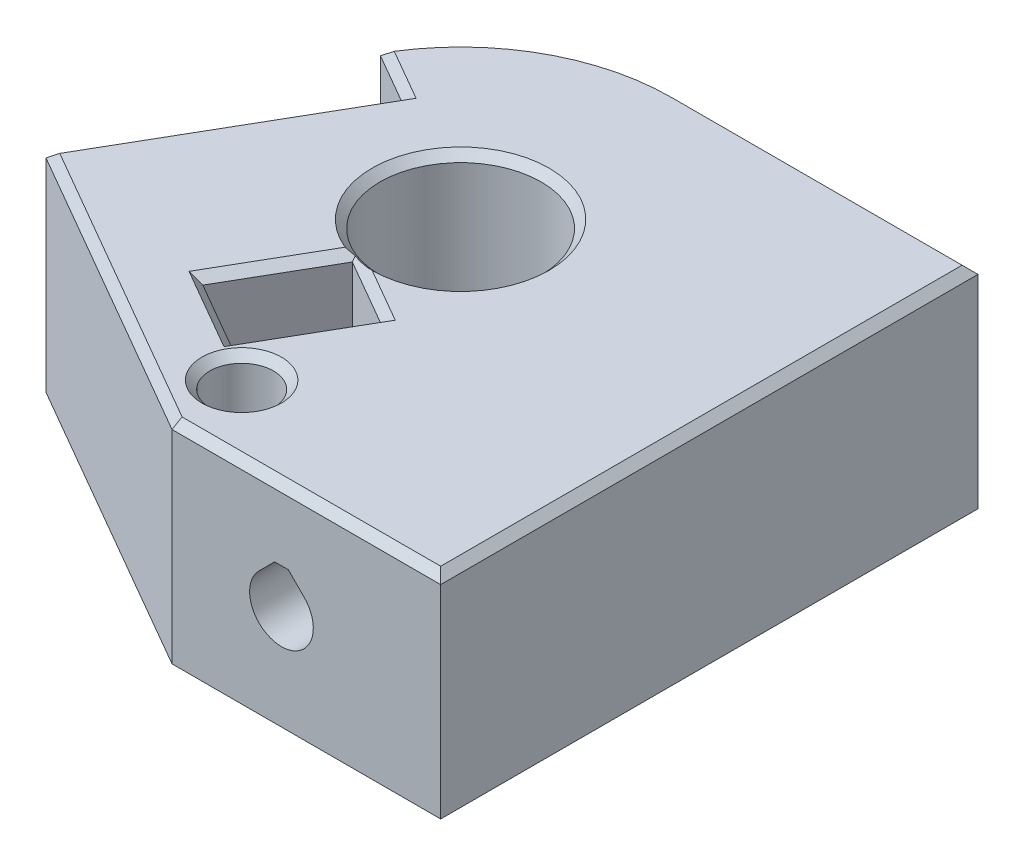
SolidWorks part; units mm, degrees
material "Custom Plastic"
ref_plane "Front Plane" through (0, 0, 0) normal (0, 0, 1) x (1, 0, 0)
ref_plane "Top Plane" through (0, 0, 0) normal (0, 1, 0) x (1, 0, 0)
ref_plane "Right Plane" through (0, 0, 0) normal (1, 0, 0) x (0, 0, -1)
sketch "Sketch1" plane through (0, 0, 0) normal (0, 1, 0) x (1, 0, 0)
  line L0 (-7.5, 0) -> (-21, 0)
  line L2 (-22.5, 24) -> (-7.5, 24) construction
  line L3 (0, 24) -> (0, 0) construction
  line L5 (-23.3922, 20.8354) -> (-21.6078, 20.8354) construction
  line L6 (-22.5, 27) -> (-7.5, 27)
  line L7 (-7.5, 0) -> (-7.5, 27)
  line L8 (-35.9814, 8.6495) -> (-21, 0)
  line L10 (-7.5, 11.5) -> (7.5, 20.5) construction
  line L11 (-7.5, 20.5) -> (7.5, 11.5) construction
  line L12 (-21.6078, 20.8354) -> (-19.6362, 18.8638) construction
  line L13 (-19.6362, 18.8638) -> (-22.5, 16) construction
  line L14 (-22.5, 16) -> (-25.3638, 18.8638) construction
  line L15 (-25.3638, 18.8638) -> (-23.3922, 20.8354) construction
  line L16 (-29.4282, 20) -> (-35.9814, 8.6495)
  line L17 (-29.4282, 20) -> (-32.0263, 21.5)
  arc A0 (-22.5, 24) -> (-29.0362, 11.3872) centre (-22.5, 16) ccw construction
  circle A1 centre (-22.5, 16) radius 4.05
  arc A2 (-22.5, 27) -> (-32.0263, 21.5) centre (-22.5, 16) ccw
  point P10 (0, 16)
  point P22 (-22.5, 20.8354)
  dimension "D4" = 8.1
  dimension "D5" = 8
  dimension "D9" = 3
  dimension "D2" = 45
  dimension "D3" = 24
  dimension "D6" = 9
  dimension "D7" = 15
  dimension "D8" = 16
  dimension "D10" = 30
  dimension "D11" = 42
extrude "Boss-Extrude1" add sketch "Sketch1" along normal blind 11
sketch "Sketch2" plane through (0, 0, 0) normal (0, 0, 1) x (1, 0, 0)
  line L0 (-22.5, 21) -> (0, 21) construction
  line L1 (-15.5, 36.5) -> (15.5, 36.5) construction
  line L2 (-15.5, 36.5) -> (-15.5, 5.5) construction
  line L3 (-15.5, 5.5) -> (15.5, 5.5) construction
  line L4 (15.5, 36.5) -> (15.5, 5.5) construction
  line L5 (-15.5, 36.5) -> (15.5, 5.5) construction
  line L6 (-15.5, 5.5) -> (15.5, 36.5) construction
  line L9 (-21, 0) -> (-7.5, 0) construction
  circle A0 centre (-15.5, 36.5) radius 1.6 construction
  circle A1 centre (15.5, 36.5) radius 1.6 construction
  circle A2 centre (15.5, 5.5) radius 1.6 construction
  circle A4 centre (0, 21) radius 11.2 construction
  circle A5 centre (-15.5, 5.5) radius 1.6
  point P0 (0, 21)
  dimension "D2" = 3.2
  dimension "D3" = 22.4
  dimension "D1" = 31
  dimension "D4" = 21
extrude "Cut-Extrude1" cut sketch "Sketch2" against normal through all
sketch "Sketch3" plane through (0, 0, -27) normal (0, 0, -1) x (-1, 0, 0)
  circle A1 centre (15.5, 5.5) radius 3.7
  circle A2 centre (15.5, 5.5) radius 1.6 construction
  dimension "D1" = 7.4
extrude "Cut-Extrude2" cut sketch "Sketch3" against normal blind 11
sketch "Sketch5" plane through (0, 11, 0) normal (0, 1, 0) x (1, 0, 0)
  line L0 (0, 0) -> (0, 3.5) construction
  line L1 (-21, 3.5) -> (21, 3.5) construction
  line L2 (-21, 0) -> (-7.5, 0) construction
  line L3 (-21, 3.5) -> (-19.8686, 4.6314) construction
  line L4 (-19.8686, 4.6314) -> (-20.6819, 5.4446) construction
  line L5 (-21, 3.5) -> (-22.1314, 4.6314) construction
  line L6 (-22.1314, 4.6314) -> (-21.3181, 5.4446) construction
  line L7 (-21.3181, 5.4446) -> (-20.6819, 5.4446) construction
  circle A0 centre (-21, 3.5) radius 1.6
  point P10 (-21, 5.4446)
  dimension "D1" = 3.2
  dimension "D2" = 42
  dimension "D3" = 3.5
extrude "Cut-Extrude4" cut sketch "Sketch5" against normal through all
ref_axis "Axis1" [suppressed] through (0, 6, -27) along (0, 0, 1)
ref_plane "Plane1" [suppressed] through (0, 6, 0) normal (0, 1, 0) x (1, 0, 0)
ref_axis "Axis2"
ref_plane "Plane2" through (0, 5.5, 0) normal (0, 1, 0) x (1, 0, 0)
sketch "Sketch11" plane through (-30.7314, 0, -17.7428) normal (-0.866, 0, -0.5) x (-0.5, 0, 0.866)
  line L0 (14.85, 5.5) -> (-14.85, 5.5) construction
  line L1 (-2.6064, 11) -> (-2.6064, 0) construction
  circle A0 centre (4.3936, 5.5) radius 1.6
  dimension "D2" = 3.2
  dimension "D1" = 7
extrude "Cut-Extrude10" cut sketch "Sketch11" against normal blind 14
sketch "Sketch10" plane through (-30.7314, 0, -17.7428) normal (-0.866, 0, -0.5) x (-0.5, 0, 0.866)
  line L0 (1.6436, 11) -> (7.1436, 11)
  line L1 (4.3936, 2.1246) -> (7.1436, 3.7123)
  line L2 (7.1436, 3.7123) -> (7.1436, 11)
  line L3 (7.1436, 6.8877) -> (4.3936, 8.4754) construction
  line L4 (4.3936, 8.4754) -> (1.6436, 6.8877) construction
  line L5 (1.6436, 11) -> (1.6436, 3.7123)
  line L6 (1.6436, 3.7123) -> (4.3936, 2.1246)
  line L7 (-2.6064, 11) -> (10.5, 11) construction
  circle A0 centre (4.3936, 5.3) radius 2.75 construction
  point P1 (4.3936, 5.5)
  dimension "D2" = 5.5
  dimension "D1" = 0.2
extrude "Cut-Extrude9" cut sketch "Sketch10" against normal blind 4 from offset 9 offset against normal yes
sketch "Sketch13" plane through (0, 0, -27) normal (0, 0, -1) x (-1, 0, 0)
  line L0 (15.5, 5.5) -> (18.1163, 8.1163)
  line L1 (18.1163, 8.1163) -> (19.94, 6.2926)
  line L2 (19.94, 6.2926) -> (19.94, 4.7074)
  line L3 (19.94, 4.7074) -> (18.1163, 2.8837)
  line L4 (18.1163, 2.8837) -> (15.5, 5.5)
  line L5 (14.85, 5.5) -> (-14.85, 5.5) construction
  circle A0 centre (15.5, 5.5) radius 3.7 construction
  arc A2 (18.45, 3.2667) -> (18.45, 7.7333) centre (15.5, 5.5) ccw construction
  point P7 (19.94, 5.5)
  point P9 (19.2, 5.5)
  dimension "D1" = 0.74
extrude "Cut-Extrude12" [suppressed] cut sketch "Sketch13" against normal up to surface (11 mm away)
sketch "Sketch14" plane through (0, 0, 0) normal (0, 0, 1) x (1, 0, 0)
  line L0 (-15.5, 5.5) -> (-16.6314, 6.6314)
  line L1 (-16.6314, 6.6314) -> (-17.42, 5.8427)
  line L2 (-17.42, 5.8427) -> (-17.42, 5.1573)
  line L3 (-17.42, 5.1573) -> (-16.6314, 4.3686)
  line L4 (-16.6314, 4.3686) -> (-15.5, 5.5)
  line L5 (14.85, 5.5) -> (-14.85, 5.5) construction
  circle A0 centre (-15.5, 5.5) radius 1.6 construction
  point P9 (-17.1, 5.5)
  dimension "D1" = 0.32
extrude "Cut-Extrude13" [suppressed] cut sketch "Sketch14" against normal through all
sketch "Sketch16" plane through (0, 0, 0) normal (0, -1, 0) x (1, 0, 0)
  line L0 (-22.5, -16) -> (-25.3638, -18.8638)
  line L1 (-25.3638, -18.8638) -> (-27.35, -16.8776)
  line L2 (-27.35, -16.8776) -> (-27.35, -15.1224)
  line L3 (-27.35, -15.1224) -> (-25.3638, -13.1362)
  line L4 (-25.3638, -13.1362) -> (-22.5, -16)
  circle A0 centre (-22.5, -16) radius 4.05 construction
  point P7 (-26.55, -16)
  dimension "D1" = 0.8
extrude "Cut-Extrude14" [suppressed] cut sketch "Sketch16" against normal through all
chamfer "Chamfer1" [suppressed] distance 0.4 angle 45
sketch "Sketch17" plane through (0, 0, -27) normal (0, 0, -1) x (-1, 0, 0)
  line L0 (15.5, 5.5) -> (18.1163, 8.1163)
  line L1 (18.1163, 8.1163) -> (16.2926, 9.94)
  line L2 (16.2926, 9.94) -> (14.7074, 9.94)
  line L3 (14.7074, 9.94) -> (12.8837, 8.1163)
  line L4 (12.8837, 8.1163) -> (15.5, 5.5)
  arc A0 (18.45, 7.7333) -> (18.45, 3.2667) centre (15.5, 5.5) ccw construction
  circle A1 centre (15.5, 5.5) radius 3.7 construction
  point P6 (15.5, 9.2)
  dimension "D1" = 0.74
extrude "Cut-Extrude15" cut sketch "Sketch17" against normal up to surface (11 mm away) up to face at (-15.125, 5.5, -16)
sketch "Sketch18" plane through (0, 0, 0) normal (0, 0, 1) x (1, 0, 0)
  line L0 (-15.5, 5.5) -> (-14.3686, 6.6314)
  line L1 (-14.3686, 6.6314) -> (-15.1573, 7.42)
  line L2 (-15.1573, 7.42) -> (-15.8427, 7.42)
  line L3 (-15.8427, 7.42) -> (-16.6314, 6.6314)
  line L4 (-16.6314, 6.6314) -> (-15.5, 5.5)
  circle A0 centre (-15.5, 5.5) radius 1.6 construction
  point P7 (-15.5, 7.1)
  dimension "D1" = 0.32
extrude "Cut-Extrude16" cut sketch "Sketch18" against normal through all
sketch "Sketch19" plane through (-30.7314, 0, -17.7428) normal (-0.866, 0, -0.5) x (-0.5, 0, 0.866)
  line L0 (4.3936, 5.5) -> (5.525, 6.6314)
  line L1 (5.525, 6.6314) -> (4.7363, 7.42)
  line L2 (4.7363, 7.42) -> (4.0509, 7.42)
  line L3 (4.0509, 7.42) -> (3.2622, 6.6314)
  line L4 (3.2622, 6.6314) -> (4.3936, 5.5)
  circle A0 centre (4.3936, 5.5) radius 1.6 construction
  circle A1 centre (4.3936, 5.5) radius 1.6 construction
  point P6 (4.3936, 7.1)
  dimension "D1" = 0.32
extrude "Cut-Extrude17" cut sketch "Sketch19" against normal up to surface (14 mm away) up to face at (-21.6038, 5.5, -5.5522)
chamfer "Chamfer2" distance 0.4 angle 45 22 edges at (-22.5, 0, -11.95) (-14.25, 0, 0) (-7.5, 0, -13.5) (-15, 0, -27) (-28, 0, -25.5263) (-30.7272, 0, -20.75) (-32.7048, 0, -14.3248) (-28.4907, 0, -4.3248) (-21, 0, -1.9) (-25.134, 11, -9.4378) (-24.7769, 11, -6.0563) (-21.6699, 11, -7.4378) (-22.0269, 11, -10.8194) (-21, 11, -1.9) (-32.7048, 11, -14.3248) (-30.7272, 11, -20.75) (-28, 11, -25.5263) (-15, 11, -27) (-7.5, 11, -13.5) (-14.25, 11, 0) (-28.4907, 11, -4.3248) (-22.5, 11, -11.95)
